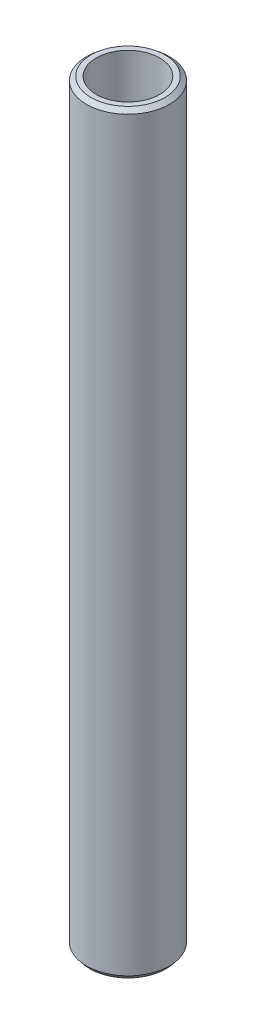
SolidWorks part; units mm, degrees
ref_plane "Front Plane" through (0, 0, 0) normal (0, 0, 1) x (1, 0, 0)
ref_plane "Top Plane" through (0, 0, 0) normal (0, 1, 0) x (1, 0, 0)
ref_plane "Right Plane" through (0, 0, 0) normal (1, 0, 0) x (0, 0, -1)
sketch "Sketch1" plane through (0, 0, 0) normal (0, 1, 0) x (1, 0, 0)
  circle A0 centre (0, 0) radius 30
  dimension "SHAFT_OD" = 60
extrude "Boss-Extrude1" add sketch "Sketch1" along normal blind 546.0417
sketch "Sketch2" plane through (0, 0, 0) normal (0, 1, 0) x (1, 0, 0)
  circle A0 centre (0, 0) radius 22.9618
  dimension "BORE_D" = 45.9236
extrude "Cut-Extrude1" cut sketch "Sketch2" along normal through all
chamfer "Chamfer1" distance 2.6798 angle 50.396 2 edges at (0, 546.0417, 30) (0, 0, 30) first distance on face at (0, 546.0417, 30) first distance on face at (0, 0, 22.9618)
